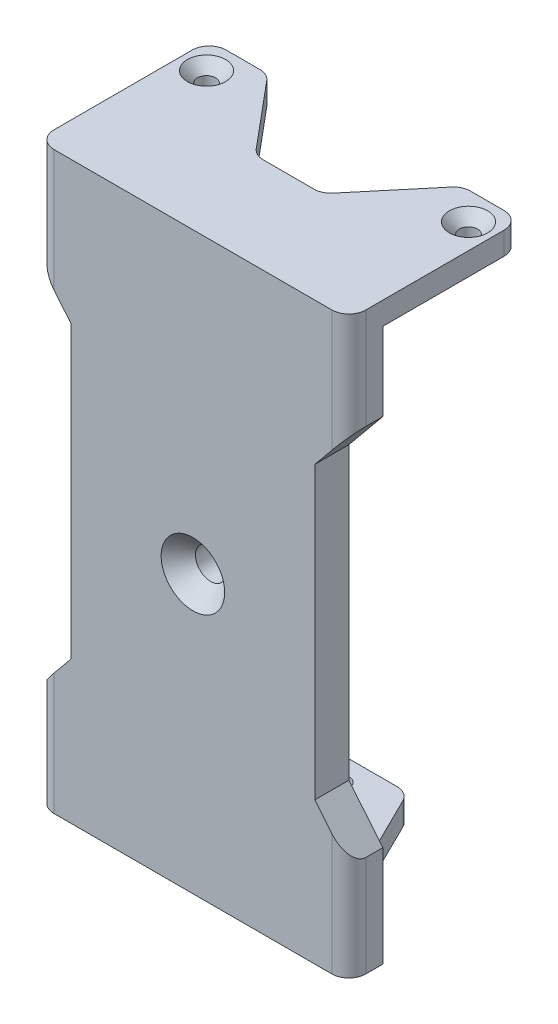
SolidWorks part; units mm, degrees
ref_plane "Front Plane" through (0, 0, 0) normal (0, 0, 1) x (1, 0, 0)
ref_plane "Top Plane" through (0, 0, 0) normal (0, 1, 0) x (1, 0, 0)
ref_plane "Right Plane" through (0, 0, 0) normal (1, 0, 0) x (0, 0, -1)
sketch "Sketch1" plane through (0, 0, 0) normal (0, 0, 1) x (1, 0, 0)
  line L0 (0, 0) -> (55, 0) construction
  line L1 (55, 0) -> (55, -93.4) construction
  line L2 (55, -93.4) -> (0, -93.4) construction
  line L3 (0, -93.4) -> (0, 0) construction
  line L7 (55, 0) -> (0, 0)
  line L8 (55, -46.7) -> (0, -46.7) construction
  line L10 (27.5, 0) -> (27.5, -102.43) construction
  line L11 (55, 0) -> (55, -13.7874)
  line L12 (55, -13.7874) -> (49, -21.0837)
  line L13 (49, -21.0837) -> (49, -72.3163)
  line L14 (55, -79.6126) -> (49, -72.3163)
  line L15 (55, -93.4) -> (55, -79.6126)
  line L16 (55, -93.4) -> (0, -93.4)
  line L17 (0, -93.4) -> (0, -79.6126)
  line L18 (0, -79.6126) -> (6, -72.3163)
  line L19 (6, -21.0837) -> (6, -72.3163)
  line L20 (0, -13.7874) -> (6, -21.0837)
  line L21 (0, 0) -> (0, -13.7874)
  circle A1 centre (48, -6) radius 4.5 construction
  point P14 (49, -46.7)
  point P16 (27.5, -93.4)
  point P24 (27.5, -93.4)
  dimension "D4" = 9
  dimension "D1" = 55
  dimension "D2" = 93.4
  dimension "D3" = 6
  dimension "D5" = 7
  dimension "D6" = 6
extrude "Boss-Extrude1" add sketch "Sketch1" along normal blind 6 contours L19 L18 L17 L16 L15 L14 L13 L12 L11 L7 L21 L20
sketch "Sketch2" plane through (0, 0, 0) normal (0, 1, 0) x (1, 0, 0)
  line L0 (0, -6) -> (0, 0)
  line L1 (0, 0) -> (0, 24.3682)
  line L2 (27.5, -6) -> (27.5, 12.073) construction
  line L3 (55, -6) -> (0, -6) construction
  line L4 (0, 24.3682) -> (10.336, 24.3682)
  line L5 (10.336, 24.3682) -> (21.6251, 10.8693)
  line L6 (21.6251, 10.8693) -> (33.3749, 10.8693)
  line L7 (55, 0) -> (55, 24.3682)
  line L8 (55, 24.3682) -> (44.664, 24.3682)
  line L9 (44.664, 24.3682) -> (33.3749, 10.8693)
  line L10 (0, -6) -> (55, -6)
  line L11 (55, -6) -> (55, 0)
  point P16 (27.5, 10.8693)
extrude "Boss-Extrude2" add sketch "Sketch2" along normal blind 4
sketch "Sketch3" plane through (0, -93.4, 0) normal (0, -1, 0) x (1, 0, 0)
  line L0 (55, 6) -> (0, 6)
  line L1 (0, 6) -> (0, 0)
  line L2 (0, 0) -> (7.9746, 0)
  line L3 (55, 0) -> (0, 0) construction
  line L4 (7.9746, 0) -> (20, -24.3649)
  line L5 (27.5, 6) -> (27.5, -18.9998) construction
  line L6 (20, -24.3649) -> (35, -24.3649)
  line L7 (55, 6) -> (55, 0)
  line L8 (55, 0) -> (47.0254, 0)
  line L9 (47.0254, 0) -> (35, -24.3649)
  line L10 (55, 0) -> (0, 0) construction
  point P16 (27.5, -24.3649)
  dimension "D1" = 15
extrude "Boss-Extrude3" add sketch "Sketch3" along normal blind 4
sketch "Sketch4" plane through (0, 0, 6) normal (0, 0, 1) x (1, 0, 0)
  line L0 (0, 4) -> (55, 4) construction
  line L1 (0, 4) -> (0, -13.7874) construction
  circle A0 centre (27.5, -48.6) radius 2.7
  dimension "D1" = 5.4
  dimension "D2" = 52.6
  dimension "D3" = 27.5
extrude "Cut-Extrude1" cut sketch "Sketch4" against normal up to surface (6 mm away) up to face at (27.5, -59.375, 0)
ref_plane "Plane1" through (0, 0, 2.85) normal (0, 0, 1) x (1, 0, 0)
sketch "Sketch5" plane through (0, 0, 2.85) normal (0, 0, 1) x (1, 0, 0)
  circle A0 centre (27.5, -48.6) radius 2.7 construction
  circle A1 centre (27.5, -48.6) radius 2.7
sketch "Sketch6" plane through (0, 0, 6) normal (0, 0, 1) x (1, 0, 0)
  circle A0 centre (27.5, -48.6) radius 5.6
  dimension "D1" = 11.2
loft "Cut-Loft1" cut profiles "Sketch6", "Sketch5" connector at (23.0345, -45.2208, 6) connector at (25.1786, -47.2212, 2.85)
sketch "Sketch7" plane through (0, 4, 0) normal (0, 1, 0) x (1, 0, 0)
  line L0 (27.5, -6) -> (27.5, 28.4444) construction
  line L1 (0, -6) -> (55, -6) construction
  line L3 (55, -6) -> (55, 24.3682) construction
  circle A0 centre (50.6, 19.5) radius 1.6
  circle A1 centre (4.4, 19.5) radius 1.6
  dimension "D1" = 3.2
  dimension "D2" = 4.4
  dimension "D3" = 25.5
extrude "Cut-Extrude2" cut sketch "Sketch7" against normal up to surface (4 mm away) up to face at (27.5, 0, -14.9015)
sketch "Sketch8" plane through (0, -97.4, 0) normal (0, -1, 0) x (1, 0, 0)
  line L0 (55, 6) -> (0, 6) construction
  circle A0 centre (27.5, -20) radius 1.6
  point P5 (27.5, 6)
  dimension "D1" = 3.2
  dimension "D2" = 26
extrude "Cut-Extrude3" cut sketch "Sketch8" against normal up to surface (4 mm away) up to face at (27.5, -93.4, -12.1825)
ref_plane "Plane2" through (0, -95.5, 0) normal (0, -1, 0) x (-1, 0, 0)
sketch "Sketch9" plane through (0, -95.5, 0) normal (0, -1, 0) x (-1, 0, 0)
  circle A0 centre (-27.5, 20) radius 1.6 construction
  circle A1 centre (-27.5, 20) radius 1.6
sketch "Sketch10" plane through (0, -97.4, 0) normal (0, -1, 0) x (1, 0, 0)
  circle A0 centre (27.5, -20) radius 3.375
  dimension "D1" = 6.75
loft "Cut-Loft2" cut profiles "Sketch10", "Sketch9" connector at (28.1449, -97.4, -16.6872) connector at (26.6572, -95.5, -21.36)
ref_plane "Plane3" through (0, 2.1, 0) normal (0, 1, 0) x (1, 0, 0)
sketch "Sketch11" plane through (0, 2.1, 0) normal (0, 1, 0) x (1, 0, 0)
  circle A0 centre (50.6, 19.5) radius 1.6 construction
  circle A1 centre (50.6, 19.5) radius 1.6
sketch "Sketch12" plane through (0, 4, 0) normal (0, 1, 0) x (1, 0, 0)
  circle A0 centre (50.6, 19.5) radius 3.375
  dimension "D2" = 6.75
loft "Cut-Loft3" cut profiles "Sketch12", "Sketch11" connector at (50.3139, 4, -22.8629) connector at (50.1018, 2.1, -21.0204)
pattern_linear "LPattern1" count 2 spacing 46.2 along (-1, 0, 0) of "Cut-Loft3"
fillet "Fillet1" radius 3 14 edges at (47.0254, -95.4, 0) (35, -95.4, -24.3649) (20, -95.4, -24.3649) (7.9746, -95.4, 0) (0, 2, -24.3682) (10.336, 2, -24.3682) (21.6251, 2, -10.8693) (33.3749, 2, -10.8693) (44.664, 2, -24.3682) (55, 2, -24.3682) (55, -88.5063, 6) (0, -88.5063, 6) (0, -4.8937, 6) (55, -4.8937, 6)
